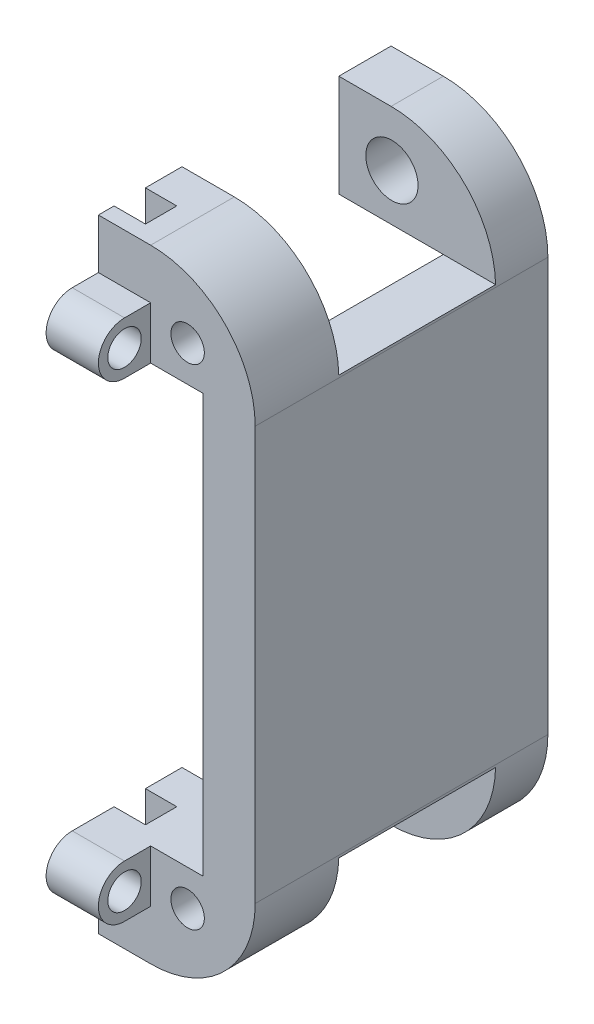
SolidWorks part; units mm, degrees
ref_plane "Front Plane" through (0, 0, 0) normal (0, 0, 1) x (1, 0, 0)
ref_plane "Top Plane" through (0, 0, 0) normal (0, 1, 0) x (1, 0, 0)
ref_plane "Right Plane" through (0, 0, 0) normal (1, 0, 0) x (0, 0, -1)
sketch "Sketch1" plane through (0, 0, 0) normal (0, 0, 1) x (1, 0, 0)
  line L0 (-5, 25) -> (10, 25)
  line L1 (-5, 20) -> (5, 20)
  line L3 (-5, -20) -> (5, -20)
  line L4 (5, 20) -> (5, -20)
  line L5 (-5, 20) -> (5, -20) construction
  line L6 (-5, -20) -> (5, 20) construction
  line L7 (10, 25) -> (10, -25)
  line L8 (-5, -25) -> (10, -25)
  line L10 (-5, 25) -> (-5, 20)
  line L11 (-10, -25) -> (10, -25) construction
  line L12 (-10, 25) -> (-10, -25) construction
  line L13 (-5, 20) -> (-5, -20) construction
  line L14 (-5, -20) -> (5, -20) construction
  line L15 (-5, -20) -> (-5, -25)
  line L16 (-10, 25) -> (10, 25) construction
  line L17 (-5, 20) -> (5, 20) construction
  point P0 (0, 0)
  dimension "D1" = 40
  dimension "D2" = 10
  dimension "D4" = 10
  dimension "D3" = 5
extrude "Boss-Extrude1" add sketch "Sketch1" along normal blind 8
sketch "Sketch2" plane through (10, 0, 0) normal (1, 0, 0) x (0, 0, -1)
  line L0 (0, 0) -> (20, 0) construction
  line L1 (0, 25) -> (0, 20) construction
  line L2 (20, -20) -> (0, -20)
  line L3 (20, -20) -> (20, 20)
  line L4 (20, 20) -> (0, 20)
  line L5 (0, -20) -> (0, 20)
  line L6 (20, -20) -> (0, 20) construction
  line L7 (20, 20) -> (0, -20) construction
  line L8 (-8, 20) -> (0, 20) construction
  point P3 (10, 0)
  dimension "D1" = 20
extrude "Boss-Extrude2" add sketch "Sketch2" against normal up to surface (5 mm away) up to face at (5, 0, 4)
ref_plane "Plane1" through (0, 0, -10) normal (0, 0, -1) x (-1, 0, 0)
sketch "Sketch3" plane through (0, 0, 8) normal (0, 0, 1) x (1, 0, 0)
  line L5 (10, 25) -> (-5, 25) construction
  line L6 (-5, 20) -> (0, 20)
  line L11 (-5, 20) -> (-5, 25)
  line L12 (-5, 25) -> (0, 25)
  line L13 (0, 20) -> (0, 25)
  line L14 (-5, 20) -> (0, 25) construction
  line L15 (-5, 25) -> (0, 20) construction
  line L16 (-5, -25) -> (10, -25) construction
  line L17 (-5, -20) -> (0, -20)
  line L18 (-5, -20) -> (-5, -25)
  line L19 (-5, -25) -> (0, -25)
  line L20 (0, -20) -> (0, -25)
  line L21 (-5, -20) -> (0, -25) construction
  line L22 (-5, -25) -> (0, -20) construction
  point P4 (-2.5, 22.5)
  point P15 (-2.5, -22.5)
  dimension "D1" = 5
  dimension "D2" = 5
extrude "Boss-Extrude3" add sketch "Sketch3" along normal blind 5
fillet "Fillet2" 2 edges at (-2.5, 25, 13) (-2.5, 20, 13) type full round first side face at (1.6667, 25, 7) second side face at (0, 20, 7) middle face at (-2.5, 22.5, 13)
fillet "Fillet3" 2 edges at (-2.5, -20, 13) (-2.5, -25, 13) type full round first side face at (0, -20, 7) second side face at (1.6667, -25, 7) middle face at (-2.5, -22.5, 13)
sketch "Sketch6" plane through (0, 0, 0) normal (1, 0, 0) x (0, 0, -1)
  circle A0 centre (-10.5, 22.5) radius 1.6
  circle A1 centre (-10.5, -22.5) radius 1.6
  dimension "D1" = 3.2
extrude "Cut-Extrude3" cut sketch "Sketch6" against normal through all
sketch "Sketch7" plane through (0, 0, -20) normal (0, 0, -1) x (-1, 0, 0)
  line L0 (5, 27.3) -> (5, 20)
  line L1 (8.58, 27.3) -> (1.42, 27.3) construction
  line L2 (5, 20) -> (-5, 20)
  line L3 (-5, 20) -> (-10, 20)
  line L4 (-10, 20) -> (-10, 27.3)
  line L5 (-10, 27.3) -> (-1.58, 27.3)
  line L6 (-1.58, 27.3) -> (-1.58, 26.5)
  line L7 (1.42, 27.3) -> (1.42, 26.5)
  line L8 (1.42, 27.3) -> (5, 27.3)
  arc A0 (-1.58, 26.5) -> (1.42, 26.5) centre (-0.08, 24.5) ccw
extrude "Boss-Extrude4" add sketch "Sketch7" against normal blind 5
ref_plane "Plane2" through (0, 0, 0) normal (0, 1, 0) x (1, 0, 0)
mirror "Mirror3" about plane through (0, 0, 0) normal (0, 1, 0) of "Boss-Extrude4"
sketch "Sketch10" plane through (0, 0, -20) normal (0, 0, -1) x (-1, 0, 0)
  line L0 (5, 29.7716) -> (-10, 29.7716)
  line L1 (-10, 27.3) -> (-10, 29.7716)
  line L2 (5, 27.3) -> (5, 29.7716)
  line L3 (5, 27.3) -> (1.42, 27.3) construction
  line L4 (1.42, 27.3) -> (1.42, 26.5) construction
  line L5 (-1.58, 26.5) -> (-1.58, 27.3) construction
  line L6 (-1.58, 27.3) -> (-10, 27.3) construction
  line L7 (5, 27.3) -> (1.42, 27.3)
  line L8 (1.42, 27.3) -> (1.42, 26.5)
  line L9 (-1.58, 26.5) -> (-1.58, 27.3)
  line L10 (-1.58, 27.3) -> (-10, 27.3)
  arc A1 (1.42, 26.5) -> (-1.58, 26.5) centre (-0.08, 24.5) ccw
  point P7 (-2.5, 29.7716)
extrude "Boss-Extrude5" add sketch "Sketch10" against normal blind 5
mirror "Mirror4" about plane through (0, 0, 0) normal (0, 1, 0) of "Boss-Extrude5"
sketch "Sketch11" plane through (0, 0, 8) normal (0, 0, 1) x (1, 0, 0)
  line L0 (10, 25) -> (10, 29.7716)
  line L1 (10, 29.7716) -> (-5, 29.7716)
  line L2 (-5, 29.7716) -> (-5, 25)
  line L3 (-5, 25) -> (10, 25)
  line L4 (10, 0) -> (14.46, 0) construction
  line L5 (10, -25) -> (10, 25) construction
  line L6 (-5, -25) -> (10, -25)
  line L7 (-5, -29.7716) -> (-5, -25)
  line L8 (10, -29.7716) -> (-5, -29.7716)
  line L9 (10, -25) -> (10, -29.7716)
extrude "Boss-Extrude6" add sketch "Sketch11" against normal up to surface (8 mm away) up to face at (3, 22, 0)
fillet "Fillet4" radius 10 1 edges at (10, 29.7716, 4)
fillet "Fillet5" radius 10 1 edges at (10, -29.7716, 4)
sketch "Sketch12" plane through (0, 0, 8) normal (0, 0, 1) x (1, 0, 0)
  line L0 (0, 20) -> (7.0711, 26.8427) construction
  line L1 (10, 0) -> (16.6872, 0) construction
  line L2 (10, -19.7716) -> (10, 19.7716) construction
  arc A0 (10, 19.7716) -> (0, 29.7716) centre (0, 19.7716) ccw construction
  circle A1 centre (3.5355, 23.4213) radius 1.6
  circle A2 centre (3.5355, -23.4213) radius 1.6
  dimension "D1" = 3.2
extrude "Cut-Extrude4" cut sketch "Sketch12" against normal blind 10
sketch "Sketch15" plane through (0, -29.7716, 0) normal (0, -1, 0) x (1, 0, 0)
  line L1 (-8, 6.5) -> (-2, 6.5)
  line L2 (-8, 6.5) -> (-8, 3.5)
  line L3 (-8, 3.5) -> (-2, 3.5)
  line L4 (-2, 6.5) -> (-2, 3.5)
  line L5 (-8, 6.5) -> (-2, 3.5) construction
  line L6 (-8, 3.5) -> (-2, 6.5) construction
  point P0 (-5, 5)
  dimension "D1" = 6
  dimension "D2" = 3
extrude "Cut-Extrude7" cut sketch "Sketch15" against normal blind 20
sketch "Sketch17" plane through (0, 29.7716, 0) normal (0, 1, 0) x (1, 0, 0)
  line L1 (-8, -3.5) -> (-2, -3.5)
  line L2 (-8, -3.5) -> (-8, -6.5)
  line L3 (-8, -6.5) -> (-2, -6.5)
  line L4 (-2, -3.5) -> (-2, -6.5)
  line L5 (-8, -3.5) -> (-2, -6.5) construction
  line L6 (-8, -6.5) -> (-2, -3.5) construction
  point P0 (-5, -5)
  dimension "D1" = 6
  dimension "D2" = 3
extrude "Cut-Extrude8" cut sketch "Sketch17" against normal blind 20
